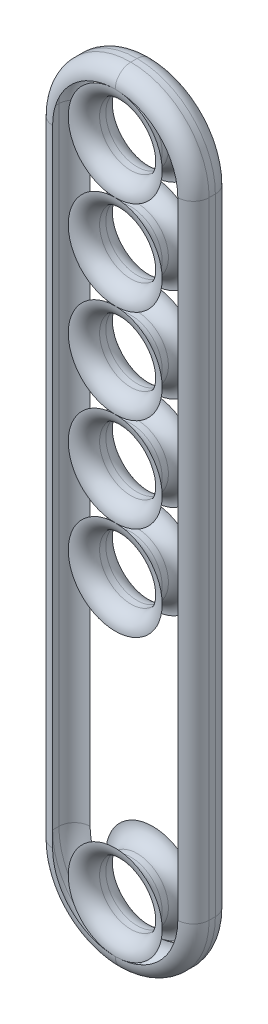
SolidWorks part; units mm, degrees
ref_plane "Front Plane" through (0, 0, 0) normal (0, 0, 1) x (1, 0, 0)
ref_plane "Top Plane" through (0, 0, 0) normal (0, 1, 0) x (1, 0, 0)
ref_plane "Right Plane" through (0, 0, 0) normal (1, 0, 0) x (0, 0, -1)
sketch "Sketch1" plane through (0, 0, 0) normal (0, 0, 1) x (1, 0, 0)
  line L1 (0, 0) -> (10, 0)
  line L2 (0, 0) -> (0, 50)
  line L3 (0, 50) -> (10, 50)
  line L4 (10, 0) -> (10, 50)
  line L5 (0, 0) -> (10, 50) construction
  line L6 (0, 50) -> (10, 0) construction
  point P4 (5, 25)
  dimension "D1" = 50
  dimension "D2" = 10
extrude "Boss-Extrude1" add sketch "Sketch1" along normal blind 2.4
sketch "Sketch2" plane through (0, 0, 2.4) normal (0, 0, 1) x (1, 0, 0)
  line L0 (5, 50) -> (5, 0) construction
  line L1 (10, 50) -> (0, 50) construction
  line L2 (0, 0) -> (10, 0) construction
  circle A0 centre (5, 46) radius 2
  circle A1 centre (5, 4) radius 2
  circle A2 centre (5, 40) radius 2
  circle A3 centre (5, 34) radius 2
  circle A4 centre (5, 28) radius 2
  circle A5 centre (5, 22) radius 2
  dimension "D1" = 4
  dimension "D2" = 4
  dimension "D3" = 4
  dimension "D4" = 4
  dimension "D5" = 5
extrude "Cut-Extrude1" cut sketch "Sketch2" against normal through all
fillet "Fillet2" radius 5 4 edges at (0, 0, 1.2) (10, 0, 1.2) (10, 50, 1.2) (0, 50, 1.2)
fillet "Fillet1" radius 1 24 edges at (0, 25, 0) (7, 4, 0) (7, 46, 0) (10, 25, 0) (10, 25, 2.4) (0, 25, 2.4) (7, 4, 2.4) (7, 46, 2.4) (8.5355, 48.5355, 0) (1.4645, 48.5355, 0) (1.4645, 1.4645, 0) (8.5355, 1.4645, 0) (1.4645, 48.5355, 2.4) (8.5355, 48.5355, 2.4) (8.5355, 1.4645, 2.4) (1.4645, 1.4645, 2.4) (7, 34, 0) (7, 40, 0) (7, 34, 2.4) (7, 40, 2.4) (7, 28, 0) (7, 22, 0) (7, 28, 2.4) (7, 22, 2.4)
